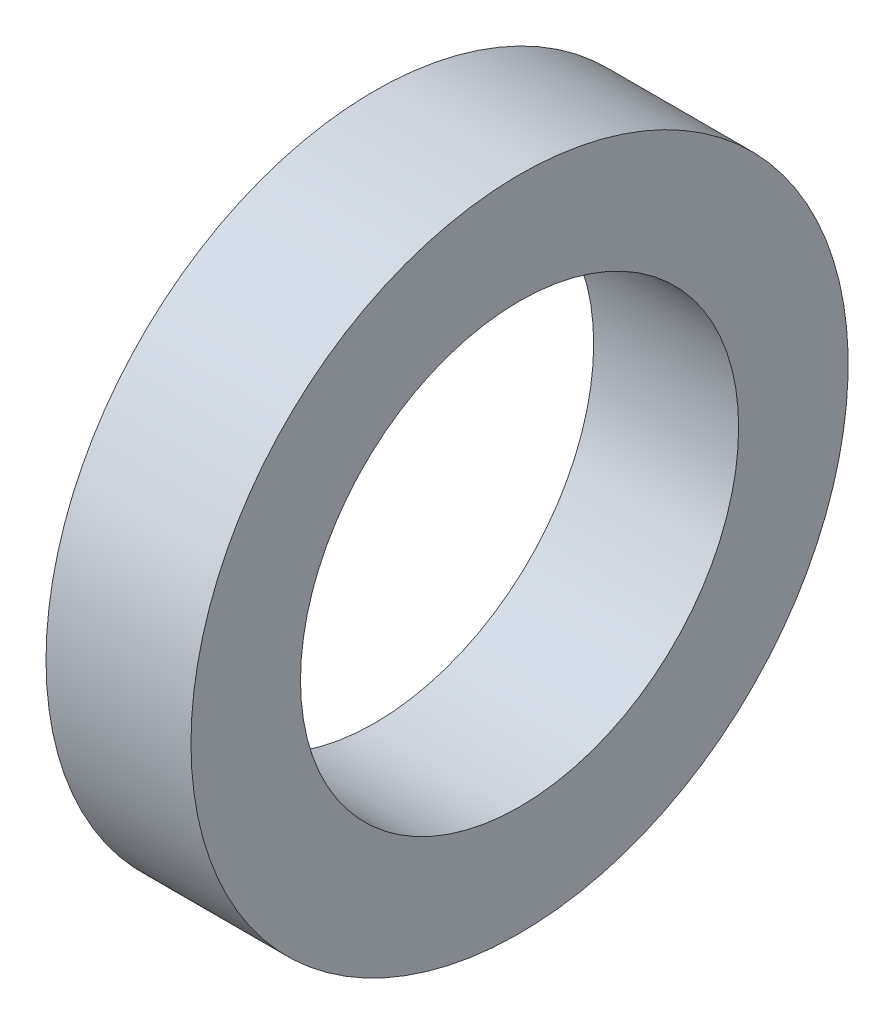
SolidWorks part; units mm, degrees
ref_plane "Front Plane" through (0, 0, 0) normal (0, 0, 1) x (1, 0, 0)
ref_plane "Top Plane" through (0, 0, 0) normal (0, 1, 0) x (1, 0, 0)
ref_plane "Right Plane" through (0, 0, 0) normal (1, 0, 0) x (0, 0, -1)
sketch "Sketch2" plane through (0, 0, 0) normal (0, 0, 1) x (1, 0, 0)
  line L0 (0, 0) -> (58.591, 0) construction
  line L2 (0, 0) -> (18.4, 0)
  line L3 (0, 0) -> (0, 2.5)
  line L4 (0, 2.5) -> (18.4, 2.5)
  line L5 (18.4, 0) -> (18.4, 2.5)
  line L6 (6, 2.5) -> (6, 6)
  line L11 (6, 6) -> (9.97, 6)
  line L16 (12.97, 6) -> (12.97, 3)
  line L17 (12.97, 3) -> (13.6304, 3)
  line L18 (13.6304, 3) -> (13.6304, 2.5)
  line L19 (13.6304, 2.5) -> (6, 2.5)
  line L22 (13.6304, 2.5) -> (16.1104, 2.5)
  line L23 (13.6304, 2.5) -> (13.6304, 4)
  line L24 (13.6304, 4) -> (16.1104, 4)
  line L25 (16.1104, 2.5) -> (16.1104, 4)
  line L27 (6, 6) -> (9.97, 6)
  line L28 (6, 6) -> (6, 9)
  line L29 (6, 9) -> (9.97, 9)
  line L30 (9.97, 6) -> (9.97, 9)
  line L31 (6, 9) -> (6, 8.25)
  line L32 (6, 8.25) -> (5, 8.25)
  line L33 (8.58, 22.001) -> (8.58, 12.476) construction
  line L34 (5, 12.476) -> (12.16, 12.476)
  line L35 (9.97, 9) -> (12.16, 9)
  line L36 (5, 7.5) -> (3, 7.5)
  line L37 (5, 8.25) -> (5, 12.476)
  line L38 (5, 7.5) -> (5, 14)
  line L39 (5, 14) -> (3, 14)
  line L40 (3, 7.5) -> (3, 14)
  line L41 (5, 22.001) -> (12.16, 22.001)
  line L42 (5, 22.001) -> (5, 30.1625)
  line L43 (5, 30.1625) -> (12.16, 30.1625)
  line L44 (12.16, 22.001) -> (12.16, 30.1625)
  line L49 (16.6304, 22.001) -> (16.6304, 7.5)
  line L51 (23.0104, 7.5) -> (23.0104, 6.5)
  line L54 (16.1104, 4) -> (13.6304, 4)
  line L56 (18.0304, 7.5) -> (23.0104, 7.5)
  line L57 (13.16, 22.001) -> (16.6304, 22.001)
  line L58 (16.1104, 3.5) -> (20.0104, 3.5)
  line L59 (29.9004, 14) -> (26.9004, 11)
  line L60 (4, 31.75) -> (18.0304, 31.75)
  line L61 (18.0304, 7.5) -> (23.0104, 7.5)
  line L62 (18.0304, 7.5) -> (18.0304, 12)
  line L63 (18.0304, 12) -> (23.0104, 12)
  line L64 (23.0104, 7.5) -> (23.0104, 12)
  line L65 (18.0304, 31.75) -> (18.0304, 12)
  line L66 (23.0104, 11) -> (26.9004, 11)
  line L67 (34.8004, 23) -> (31.3004, 19.5)
  line L68 (35.8004, 31) -> (38.7904, 33.99)
  line L69 (29.9004, 14) -> (29.9004, 15)
  line L70 (29.9004, 15) -> (22.9304, 15)
  line L71 (22.9304, 15) -> (21.0304, 15)
  line L72 (18.0304, 7.5) -> (16.6304, 7.5)
  line L73 (21.0304, 15) -> (21.0304, 43)
  line L74 (20.0304, 40) -> (10.0704, 40)
  line L75 (10.0704, 40) -> (4, 40)
  line L76 (21.0304, 43) -> (20.0304, 43)
  line L77 (22.9304, 15) -> (29.9004, 15)
  line L78 (22.9304, 15) -> (22.9304, 21)
  line L79 (22.9304, 21) -> (29.9004, 21)
  line L80 (29.9004, 15) -> (29.9004, 21)
  line L81 (10.0704, 40) -> (20.0304, 40)
  line L82 (10.0704, 40) -> (10.0704, 50)
  line L83 (10.0704, 50) -> (20.0304, 50)
  line L84 (20.0304, 40) -> (20.0304, 50)
  line L85 (4, 40) -> (4, 31.75)
  line L86 (12.97, 3) -> (12.97, 2.5)
  line L87 (31.3004, 19.5) -> (29.9004, 19.5)
  line L88 (21.51, 63.5) -> (21.51, 44)
  line L89 (21.51, 63.5) -> (25.9304, 63.5)
  line L90 (25.9304, 63.5) -> (25.9304, 25)
  line L91 (27.8304, 25) -> (25.9304, 25)
  line L92 (10.0704, 48) -> (9, 48)
  line L93 (9, 48) -> (9, 53.476)
  line L94 (9, 53.476) -> (20.0304, 53.476)
  line L95 (20.0304, 53.476) -> (20.0304, 50)
  line L96 (14.5152, 63.001) -> (14.5152, 53.476) construction
  line L97 (9, 63.001) -> (20.0304, 63.001)
  line L98 (9, 63.001) -> (9, 68.2625)
  line L99 (9, 68.2625) -> (20.0304, 68.2625)
  line L100 (20.0304, 63.001) -> (20.0304, 68.2625)
  line L101 (12.97, 6) -> (11.97, 6)
  line L102 (9, 42.5) -> (5, 42.5)
  line L103 (9, 42.5) -> (9, 55)
  line L104 (9, 55) -> (5, 55)
  line L105 (5, 42.5) -> (5, 55)
  line L106 (9.97, 6) -> (10.87, 6)
  line L107 (27.8304, 25) -> (34.8004, 25)
  line L108 (34.8004, 25) -> (34.8004, 23)
  line L109 (0, 0) -> (-2, 0)
  line L110 (0, 0) -> (0, 11)
  line L111 (27.8304, 25) -> (34.8004, 25)
  line L112 (27.8304, 25) -> (27.8304, 32.5)
  line L113 (27.8304, 32.5) -> (34.8004, 32.5)
  line L114 (34.8004, 25) -> (34.8004, 32.5)
  line L115 (35.8004, 31) -> (34.8004, 31)
  line L116 (27.8304, 32.5) -> (27.8304, 64.5)
  line L117 (21.1827, 74.025) -> (6.8477, 74.025)
  line L118 (6.8477, 74.025) -> (6.8477, 76.2)
  line L119 (38.7904, 47.29) -> (30.8304, 55.25)
  line L120 (0, 11) -> (-2, 11)
  line L121 (38.7904, 43.815) -> (30.8529, 43.815)
  line L123 (-4.8, 69.85) -> (1.55, 76.2)
  line L124 (38.7904, 47.29) -> (38.7904, 33.99)
  line L125 (-2, 0) -> (-2, 11)
  line L126 (38.7904, 37.465) -> (30.8529, 37.465)
  line L127 (30.8529, 43.815) -> (30.8529, 37.465)
  line L128 (6, 2.5) -> (6, 0)
  line L129 (0, 63.5) -> (0, 30)
  line L132 (5, 63.5) -> (0, 63.5)
  line L136 (-1.8, 30) -> (-11.76, 30)
  line L138 (-13.76, 25.4) -> (-2, 25.4)
  line L139 (-2, 25.4) -> (-2, 11.5)
  line L140 (27.8304, 64.5) -> (21.1827, 64.5)
  line L141 (-1.8, 30) -> (-11.76, 30)
  line L142 (-1.8, 30) -> (-1.8, 39)
  line L143 (-1.8, 39) -> (-11.76, 39)
  line L144 (-11.76, 30) -> (-11.76, 39)
  line L145 (21.1827, 64.5) -> (21.1827, 74.025)
  line L146 (-12.76, 37) -> (-12.76, 47.29)
  line L147 (-12.76, 37) -> (-11.76, 37)
  line L148 (30.8304, 55.25) -> (30.8304, 76.2)
  line L149 (11.97, 6) -> (11.97, 5.45)
  line L154 (-2, 11.5) -> (1, 11.5)
  line L155 (5, 60.6197) -> (24.05, 60.6197)
  line L160 (5, 60.6197) -> (5, 55.8572)
  line L161 (5, 55.8572) -> (24.05, 55.8572)
  line L166 (24.05, 60.6197) -> (24.05, 55.8572)
  line L167 (5, 60.6197) -> (24.05, 55.8572) construction
  line L172 (5, 55.8572) -> (24.05, 60.6197) construction
  line L173 (24.05, 62.2072) -> (25.9304, 62.2072)
  line L174 (11.97, 5.45) -> (10.87, 5.45)
  line L175 (10.87, 6) -> (10.87, 5.45)
  line L176 (24.05, 62.2072) -> (24.05, 54.2697)
  line L177 (24.05, 54.2697) -> (25.9304, 54.2697)
  line L178 (25.9304, 62.2072) -> (25.9304, 54.2697)
  line L179 (24.05, 62.2072) -> (25.9304, 54.2697) construction
  line L180 (24.05, 54.2697) -> (25.9304, 62.2072) construction
  line L181 (3, 19.6197) -> (15.7, 19.6197)
  line L182 (3, 19.6197) -> (3, 14.8572)
  line L183 (3, 14.8572) -> (15.7, 14.8572)
  line L184 (15.7, 19.6197) -> (15.7, 14.8572)
  line L185 (3, 19.6197) -> (15.7, 14.8572) construction
  line L186 (3, 14.8572) -> (15.7, 19.6197) construction
  line L187 (15.7, 21.2072) -> (16.6304, 21.2072)
  line L188 (15.7, 21.2072) -> (15.7, 13.2697)
  line L189 (15.7, 13.2697) -> (16.6304, 13.2697)
  line L190 (16.6304, 21.2072) -> (16.6304, 13.2697)
  line L191 (15.7, 21.2072) -> (16.6304, 13.2697) construction
  line L192 (15.7, 13.2697) -> (16.6304, 21.2072) construction
  line L193 (1, 11.5) -> (1, 6.5)
  line L194 (1, 6.5) -> (3, 6.5)
  line L195 (23.0104, 6.5) -> (20.0104, 3.5)
  line L196 (5, 63.5) -> (5, 42.5)
  line L197 (5, 42.5) -> (3, 42.5)
  line L198 (3, 42.5) -> (3, 6.5)
  line L199 (6, 0) -> (12.97, 0)
  line L200 (12.97, 0) -> (12.97, 2.5)
  line L201 (18.0304, 31.75) -> (18.0304, 35.875)
  line L202 (18.0304, 35.875) -> (21.0304, 35.875)
  line L203 (30.8304, 76.2) -> (6.8477, 76.2)
  line L204 (3.4027, 69.85) -> (7.8477, 69.85) construction
  line L205 (7.8477, 67.4687) -> (26.8977, 67.4688)
  line L206 (7.8477, 74.025) -> (7.8477, 64.5)
  line L207 (7.8477, 64.5) -> (-1.8, 64.5)
  line L208 (-1.8, 64.5) -> (-1.8, 39)
  line L209 (-12.76, 47.29) -> (-4.8, 55.25)
  line L210 (-4.8, 55.25) -> (-4.8, 69.85)
  line L211 (7.8477, 67.4687) -> (7.8477, 72.2313)
  line L212 (7.8477, 72.2313) -> (26.8977, 72.2313)
  line L213 (26.8977, 67.4688) -> (26.8977, 72.2313)
  line L214 (26.8977, 73.8187) -> (30.8304, 73.8187)
  line L215 (26.8977, 73.8187) -> (26.8977, 65.8813)
  line L216 (26.8977, 65.8813) -> (30.8304, 65.8813)
  line L217 (30.8304, 73.8187) -> (30.8304, 65.8813)
  line L218 (3.4027, 72.2313) -> (25.6277, 72.2313)
  line L219 (3.4027, 72.2313) -> (3.4027, 67.4687)
  line L220 (3.4027, 67.4687) -> (25.6277, 67.4687)
  line L221 (25.6277, 72.2313) -> (25.6277, 67.4687)
  line L222 (25.6277, 69.85) -> (21.1827, 69.85) construction
  line L223 (21.51, 44) -> (22.9304, 44)
  line L224 (22.9304, 44) -> (22.9304, 21)
  line L225 (13.6304, 4) -> (13.6304, 12.2697)
  line L226 (13.6304, 12.2697) -> (13.16, 12.2697)
  line L227 (13.16, 12.2697) -> (13.16, 22.001)
  line L228 (12.16, 9) -> (12.16, 12.476)
  line L229 (-1.8, 30) -> (0, 30)
  line L230 (9, 65.6317) -> (3.4027, 65.6317) construction
  line L231 (20.0304, 65.6317) -> (25.6277, 65.6317) construction
  line L232 (1.55, 76.2) -> (6.8477, 76.2)
  line L233 (-11.76, 30) -> (-13.76, 30)
  line L234 (-13.76, 30) -> (-13.76, 25.4)
  circle A0 centre (26.8804, 25.95) radius 0.95
  circle A1 centre (21.9804, 15.95) radius 0.95
  circle A2 centre (17.3304, 8.2) radius 0.7
  circle A3 centre (10.42, 6.45) radius 0.45
  circle A4 centre (-0.9, 30.9) radius 0.9
  point P7 (24.9902, 58.2385)
  point P131 (16.1652, 17.2385)
  point P135 (14.525, 58.2385)
  point P146 (9.35, 17.2385)
sketch "Sketch3" plane through (0, 0, 0) normal (0, 0, 1) x (1, 0, 0)
  line L0 (6, 9) -> (9.97, 9) construction
  line L1 (9.97, 6) -> (9.97, 9) construction
  line L2 (6, 6) -> (9.97, 6) construction
  line L3 (6, 6) -> (6, 9) construction
  line L4 (6, 9) -> (9.97, 9)
  line L5 (9.97, 6) -> (9.97, 9)
  line L6 (6, 6) -> (9.97, 6)
  line L7 (6, 6) -> (6, 9)
revolve "Revolve1" add sketch "Sketch3" angle 360 about L0
